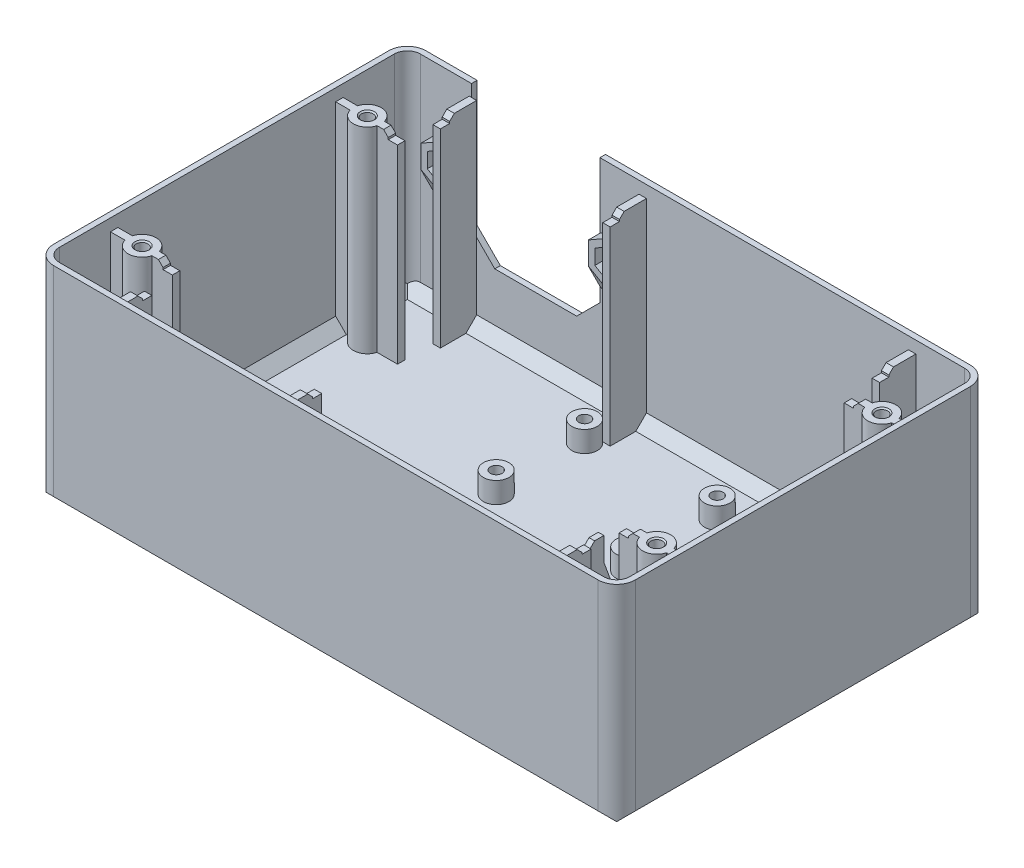
SolidWorks part; units mm, degrees
ref_plane "Ebene vorne" through (0, 0, 0) normal (0, 0, 1) x (1, 0, 0)
ref_plane "Ebene oben" through (0, 0, 0) normal (0, 1, 0) x (1, 0, 0)
ref_plane "Ebene rechts" through (0, 0, 0) normal (1, 0, 0) x (0, 0, -1)
sketch "Skizze1" plane through (0, 0, 0) normal (0, 1, 0) x (1, 0, 0)
  line L1 (-62.5, -40) -> (62.5, -40)
  line L2 (-62.5, -40) -> (-62.5, 40)
  line L3 (-62.5, 40) -> (62.5, 40)
  line L4 (62.5, -40) -> (62.5, 40)
  line L5 (-62.5, -40) -> (62.5, 40) construction
  line L6 (-62.5, 40) -> (62.5, -40) construction
  point P0 (0, 0)
  dimension "D1" = 125
  dimension "D2" = 80
extrude "Aufsatz-Linear austragen1" add sketch "Skizze1" along normal blind 46
fillet "Verrundung1" radius 3 4 edges at (0, 0, -40) (-62.5, 0, 0) (0, 0, 40) (62.5, 0, 0) profile chamfer
fillet "Verrundung2" radius 4 4 edges at (62.5, 24.5, 40) (62.5, 24.5, -40) (-62.5, 24.5, -40) (-62.5, 24.5, 40)
shell "Wandung1" thickness 1.2 removed face at (0, 46, 0)
sketch "Skizze2" plane through (0, 1.2, 0) normal (0, 1, 0) x (1, 0, 0)
  line L0 (31.05, -19.05) -> (31.05, -5.3) construction
  line L1 (14.8, -5.3) -> (47.3, -5.3) construction
  line L2 (14.8, -5.3) -> (14.8, -32.8) construction
  line L3 (14.8, -32.8) -> (47.3, -32.8) construction
  line L4 (47.3, -5.3) -> (47.3, -32.8) construction
  line L5 (14.8, -5.3) -> (47.3, -32.8) construction
  line L6 (14.8, -32.8) -> (47.3, -5.3) construction
  line L7 (20.85, -2.3) -> (22.05, -2.3)
  line L8 (20.85, -2.3) -> (20.85, -5.3)
  line L9 (20.85, -5.3) -> (22.05, -5.3)
  line L10 (22.05, -2.3) -> (22.05, -5.3)
  line L11 (31.05, -19.05) -> (14.8, -19.05) construction
  line L12 (61.3, -38.8) -> (61.3, 38.8) construction
  line L13 (-61.3, -38.8) -> (61.3, -38.8) construction
  line L14 (41.25, -5.3) -> (40.05, -5.3)
  line L15 (41.25, -2.3) -> (41.25, -5.3)
  line L16 (40.05, -2.3) -> (40.05, -5.3)
  line L17 (41.25, -2.3) -> (40.05, -2.3)
  line L18 (50.3, -18.45) -> (50.3, -19.65)
  line L19 (14.8, -18.45) -> (11.8, -18.45)
  line L20 (14.8, -18.45) -> (14.8, -19.65)
  line L21 (14.8, -19.65) -> (11.8, -19.65)
  line L22 (11.8, -18.45) -> (11.8, -19.65)
  line L23 (47.3, -18.45) -> (47.3, -19.65)
  line L24 (47.3, -19.65) -> (50.3, -19.65)
  line L25 (47.3, -18.45) -> (50.3, -18.45)
  line L26 (41.25, -35.8) -> (40.05, -35.8)
  line L27 (40.05, -35.8) -> (40.05, -32.8)
  line L28 (41.25, -35.8) -> (41.25, -32.8)
  line L29 (41.25, -32.8) -> (40.05, -32.8)
  line L30 (22.05, -35.8) -> (22.05, -32.8)
  line L31 (20.85, -32.8) -> (22.05, -32.8)
  line L32 (20.85, -35.8) -> (20.85, -32.8)
  line L33 (20.85, -35.8) -> (22.05, -35.8)
  point P0 (31.05, -19.05)
  dimension "D1" = 1.2
  dimension "D2" = 3
  dimension "D3" = 18
  dimension "D4" = 32.5
  dimension "D5" = 27.5
  dimension "D6" = 14
  dimension "D7" = 6
extrude "Aufsatz-Linear austragen2" add sketch "Skizze2" along normal blind 16
sketch "Skizze3" plane through (0, 0, 19.65) normal (0, 0, 1) x (1, 0, 0)
  line L0 (50.3, 17.2) -> (61.3, 11.2)
  line L1 (61.3, 46) -> (61.3, 1.2) construction
  dimension "D1" = 6
rib "Verstärkungsrippe1" sketch "Skizze3" sketch "Skizze3" thickness 1.2 extrusion direction parallel to sketch draft on no parameters "D1"=1.2
sketch "Skizze4" plane through (41.25, 0, 0) normal (1, 0, 0) x (0, 0, -1)
  line L0 (-35.8, 17.2) -> (-38.8, 11.2)
  line L1 (-38.8, 46) -> (-38.8, 1.2) construction
  dimension "D1" = 6
rib "Verstärkungsrippe3" sketch "Skizze4" sketch "Skizze4" thickness 1.2 extrusion direction parallel to sketch draft on no parameters "D1"=1.2
sketch "Skizze6" plane through (0, 1.2, 0) normal (0, 1, 0) x (1, 0, 0)
  line L0 (15.3, 9.8) -> (-13.2, 9.8) construction
  line L1 (-13.2, 9.8) -> (-13.2, 28.8) construction
  line L2 (-13.2, 28.8) -> (15.3, 28.8) construction
  line L3 (15.3, 28.8) -> (15.3, 9.8) construction
  line L4 (58.5, 38.8) -> (-58.5, 38.8) construction
  line L5 (61.3, -18.45) -> (61.3, 36) construction
  circle A0 centre (-13.2, 9.8) radius 2.75
  circle A1 centre (-13.2, 28.8) radius 2.75
  circle A2 centre (15.3, 9.8) radius 2.75
  circle A3 centre (15.3, 28.8) radius 2.75
  dimension "D3" = 5.5
  dimension "D1" = 19
  dimension "D2" = 10
  dimension "D4" = 46
  dimension "D5" = 28.5
extrude "Aufsatz-Linear austragen3" add sketch "Skizze6" along normal blind 4.5
hole_wizard "M3 Gewindebohrung1" positions "Skizze7" profile "Skizze8" tap size "M3" standard "DIN"
sketch "Skizze7" plane through (0, 5.7, 0) normal (0, 1, 0) x (1, 0, 0)
  point P0 (-13.2, 9.8)
  point P3 (-13.2, 28.8)
  point P6 (15.3, 9.8)
  point P9 (15.3, 28.8)
sketch "Skizze8" plane through (-13.2, 5.7, -9.8) normal (1, 0, 0) x (0, 0, 1)
  line L0 (0, 0) -> (0, 5.2511)
  line L1 (0, 5.2511) -> (1.25, 4.5)
  line L2 (1.25, 4.5) -> (1.25, 0)
  line L5 (1.25, 0) -> (0, 0)
  line L10 (0, 5.2511) -> (-1.25, 4.5) construction
  line L11 (0, -6.35) -> (0, 107.95) construction
  dimension "Bohrerdurchmesser" = 2.5
  dimension "Bohrungstiefe" = 4.5
  dimension "Spitzenwinkel" = 118
cosmetic thread "Bohrungsgewinde1" parameters "D1"=4.5, "D2"=3
cosmetic thread "Bohrungsgewinde2" parameters "D1"=4.5, "D2"=3
cosmetic thread "Bohrungsgewinde3" parameters "D1"=4.5, "D2"=3
cosmetic thread "Bohrungsgewinde4" parameters "D1"=4.5, "D2"=3
sketch "Skizze9" plane through (0, 0, -38.8) normal (0, 0, 1) x (1, 0, 0)
  line L0 (-58.5, 46) -> (58.5, 46) construction
  line L1 (-47.5, 46) -> (-19.9, 46)
  line L2 (-47.5, 46) -> (-47.5, 14)
  line L3 (-47.5, 14) -> (-19.9, 14)
  line L4 (-19.9, 46) -> (-19.9, 14)
  line L9 (-58.5, 3) -> (-58.5, 46) construction
  point P10 (-54.2481, 52.9401)
  dimension "D1" = 27.6
  dimension "D2" = 11
  dimension "D3" = 32
extrude "Schnitt-Linear austragen1" cut sketch "Skizze9" against normal up to next
chamfer "Fase1" distance 5 angle 45 2 edges at (-19.9, 14, -39.4) (-47.5, 14, -39.4)
hole_wizard "Durchgangsloch für M31" positions "Skizze10" profile "Skizze11" hole size "M3" standard "DIN" end condition up to next
sketch "Skizze10" plane through (0, 0, -40) normal (0, 0, 1) x (1, 0, 0)
  point P0 (-51.7, 29.5)
  point P2 (-15.7, 29.5)
  point P15 (-14.7, 23.5)
  point P17 (-50.7, 23.5)
sketch "Skizze11" plane through (-51.7, 29.5, -40) normal (1, 0, 0) x (0, 1, 0)
  line L0 (0, 0) -> (0, 1.2)
  line L1 (0, 1.2) -> (1.7, 1.2)
  line L2 (1.7, 1.2) -> (1.7, 0)
  line L5 (1.7, 0) -> (0, 0)
  line L11 (0, -6.35) -> (0, 107.95) construction
  dimension "Bohrerdurchmesser" = 3.4
  dimension "Bohrungstiefe" = 1.2
sketch "Skizze12" plane through (0, 0, -38.8) normal (0, 0, -1) x (-1, 0, 0)
  line L1 (18.5, 27.8834) -> (18.5, 31.1166)
  line L2 (18.5, 31.1166) -> (15.7, 32.7332)
  line L3 (15.7, 32.7332) -> (12.9, 31.1166)
  line L4 (12.9, 31.1166) -> (12.9, 27.8834)
  line L5 (12.9, 27.8834) -> (15.7, 26.2668)
  line L6 (15.7, 26.2668) -> (18.5, 27.8834)
  line L7 (19.9, 19) -> (19.9, 46) construction
  line L8 (19.9, 31.9249) -> (15.7, 34.3497)
  line L9 (15.7, 34.3497) -> (11.5, 31.9249)
  line L10 (11.5, 31.9249) -> (11.5, 27.0751)
  line L11 (11.5, 27.0751) -> (15.7, 24.6503)
  line L12 (15.7, 24.6503) -> (19.9, 27.0751)
  line L13 (19.9, 27.0751) -> (19.9, 31.9249)
  circle A0 centre (15.7, 29.5) radius 2.8 construction
  circle A1 centre (15.7, 29.5) radius 4.2 construction
  dimension "D1" = 5.6
extrude "Aufsatz-Linear austragen4" add sketch "Skizze12" against normal blind 2.5
ref_plane "Ebene2" through (-33.7, 0, 0) normal (1, 0, 0) x (0, 0, -1)
mirror "Spiegeln2" about plane through (-33.7, 0, 0) normal (1, 0, 0) of "Aufsatz-Linear austragen4"
ref_plane "Ebene3" through (0, 42, 0) normal (0, 1, 0) x (1, 0, 0)
sketch "Skizze14" plane through (0, 42, 0) normal (0, 1, 0) x (1, 0, 0)
  line L0 (-61.3, 36) -> (-61.3, -36) construction
  line L1 (50, 33) -> (-50, 33) construction
  line L2 (50, 33) -> (50, -33) construction
  line L3 (50, -33) -> (-50, -33) construction
  line L4 (-50, 33) -> (-50, -33) construction
  line L5 (50, 33) -> (-50, -33) construction
  line L6 (50, -33) -> (-50, 33) construction
  line L7 (-48, -25) -> (-61.3, -25)
  line L8 (-48, -25) -> (-48, -23.4)
  line L9 (-48, -23.4) -> (-61.3, -23.4)
  line L10 (-61.3, -25) -> (-61.3, -23.4)
  line L11 (0, 0) -> (-50, 0) construction
  line L12 (0, 0) -> (0, -33) construction
  line L17 (-58.5, -38.8) -> (58.5, -38.8) construction
  line L18 (-46.4, -38.8) -> (-48, -38.8)
  line L19 (-46.4, -38.8) -> (-46.4, -31)
  line L20 (-46.4, -31) -> (-48, -31)
  line L21 (-48, -38.8) -> (-48, -31)
  line L23 (-11.5, 36.3) -> (-11.5, 38.8) construction
  line L24 (-9.9, -38.8) -> (-11.5, -38.8)
  line L25 (-9.9, -38.8) -> (-9.9, -31)
  line L26 (-9.9, -31) -> (-11.5, -31)
  line L27 (-11.5, -38.8) -> (-11.5, -31)
  line L28 (-58.5, -38.8) -> (58.5, -38.8) construction
  line L29 (46.4, -31) -> (48, -31)
  line L30 (48, -38.8) -> (48, -31)
  line L31 (46.4, -38.8) -> (48, -38.8)
  line L32 (46.4, -38.8) -> (46.4, -31)
  line L33 (61.3, -25) -> (61.3, -23.4)
  line L34 (48, -23.4) -> (61.3, -23.4)
  line L35 (48, -25) -> (48, -23.4)
  line L36 (48, -25) -> (61.3, -25)
  point P0 (0, 0)
  dimension "D1" = 100
  dimension "D2" = 66
  dimension "D3" = 2
  dimension "D4" = 8
  dimension "D5" = 1.6
  dimension "D6" = 2
  dimension "D7" = 2
extrude "Aufsatz-Linear austragen5" add sketch "Skizze14" against normal up to next
sketch "Skizze15" plane through (0, 42, 0) normal (0, 1, 0) x (1, 0, 0)
  line L0 (46.4, -38.8) -> (46.4, -31) construction
  line L1 (48, -38.8) -> (46.4, -38.8)
  line L2 (48, -38.8) -> (48, -33)
  line L3 (48, -33) -> (46.4, -33)
  line L4 (46.4, -38.8) -> (46.4, -33)
  line L5 (50, -33) -> (-50, -33) construction
  line L6 (-11.5, -38.8) -> (-11.5, -31) construction
  line L7 (-9.9, -38.8) -> (-11.5, -38.8)
  line L8 (-9.9, -38.8) -> (-9.9, -33)
  line L9 (-9.9, -33) -> (-11.5, -33)
  line L10 (-11.5, -38.8) -> (-11.5, -33)
  line L11 (-48, -38.8) -> (-48, -31) construction
  line L12 (-46.4, -38.8) -> (-48, -38.8)
  line L13 (-46.4, -38.8) -> (-46.4, -33)
  line L14 (-46.4, -33) -> (-48, -33)
  line L15 (-48, -38.8) -> (-48, -33)
  line L16 (-48, -25) -> (-61.3, -25) construction
  line L17 (-50, -25) -> (-61.3, -25)
  line L18 (-50, -25) -> (-50, -23.4)
  line L19 (-50, -23.4) -> (-61.3, -23.4)
  line L20 (-61.3, -25) -> (-61.3, -23.4)
  line L21 (-50, 33) -> (-50, -33) construction
  line L22 (48, -23.4) -> (61.3, -23.4) construction
  line L23 (61.3, -25) -> (50, -25)
  line L24 (61.3, -25) -> (61.3, -23.4)
  line L25 (61.3, -23.4) -> (50, -23.4)
  line L26 (50, -25) -> (50, -23.4)
  line L27 (50, 33) -> (50, -33) construction
extrude "Aufsatz-Linear austragen6" add sketch "Skizze15" along normal blind 1.4
chamfer "Fase2" distance 1 angle 45 5 edges at (-50, 43.4, 24.2) (-47.2, 43.4, 33) (-10.7, 43.4, 33) (47.2, 43.4, 33) (50, 43.4, 24.2)
mirror "Spiegeln3" about plane through (0, 0, 0) normal (0, 0, 1) of "Fase2", "Aufsatz-Linear austragen5", "Aufsatz-Linear austragen6"
ref_plane "Ebene1" through (31.05, 0, 0) normal (1, 0, 0) x (0, 0, -1)
sketch "Skizze16" plane through (41.25, 0, 0) normal (1, 0, 0) x (0, 0, -1)
  line L2 (-2.3, 12.2) -> (1.7, 1.2)
  line L4 (23.4, 1.2) -> (-18.45, 1.2) construction
  line L5 (-2.3, 17.2) -> (-2.3, 1.2) construction
  dimension "D1" = 5
  dimension "D2" = 4
rib "Verstärkungsrippe4" sketch "Skizze16" sketch "Skizze16" thickness 1.2 extrusion direction parallel to sketch draft on no parameters "D1"=1.2
sketch "Skizze17" plane through (0, 0, 18.45) normal (0, 0, -1) x (-1, 0, 0)
  line L0 (-11.8, 17.2) -> (0.2, 1.2)
  line L1 (-40.05, 1.2) -> (9.9, 1.2) construction
  dimension "D1" = 12
rib "Verstärkungsrippe5" sketch "Skizze17" sketch "Skizze17" thickness 1.2 extrusion direction parallel to sketch draft on no parameters "D1"=1.2
chamfer "Fase3" distance 1 angle 45 6 edges at (14.8, 17.2, 19.05) (21.45, 17.2, 32.8) (40.65, 17.2, 32.8) (47.3, 17.2, 19.05) (21.45, 17.2, 5.3) (40.65, 17.2, 5.3)
mirror "Spiegeln1" about plane through (31.05, 0, 0) normal (1, 0, 0) of "Verstärkungsrippe3", "Verstärkungsrippe4"
sketch "Skizze18" plane through (-62.5, 0, 0) normal (-1, 0, 0) x (0, 0, 1)
  line L0 (0, 0) -> (0, 46) construction
  line L1 (-36, 46) -> (36, 46) construction
  line L2 (8, 23.8769) -> (8, 46)
  line L3 (8, 46) -> (-8, 46)
  line L4 (-8, 23.8769) -> (-8, 46)
  arc A0 (-8, 23.8769) -> (8, 23.8769) centre (0, 28) ccw
  dimension "D1" = 9
  dimension "D2" = 8
  dimension "D3" = 18
extrude "Schnitt-Linear austragen2" [suppressed] cut sketch "Skizze18" against normal up to next
sketch "Skizze19" plane through (0, 43.4, 0) normal (0, 1, 0) x (1, 0, 0)
  line L0 (-61.3, -24.2) -> (-55.3, -24.2) construction
  line L1 (-61.3, -23.4) -> (-61.3, -25) construction
  line L2 (-61.3, 24.2) -> (-55.3, 24.2) construction
  line L3 (-61.3, 23.4) -> (-61.3, 25) construction
  line L4 (-55.3, 24.2) -> (-55.3, -24.2) construction
  line L5 (55.3, -24.2) -> (61.3, -24.2) construction
  line L6 (61.3, -25) -> (61.3, -23.4) construction
  line L7 (61.3, 24.2) -> (55.3, 24.2) construction
  line L8 (61.3, 25) -> (61.3, 23.4) construction
  line L9 (55.3, -24.2) -> (55.3, 24.2) construction
  circle A0 centre (-55.3, -24.2) radius 3
  circle A1 centre (-55.3, 24.2) radius 3
  circle A2 centre (55.3, 24.2) radius 3
  circle A3 centre (55.3, -24.2) radius 3
  dimension "D2" = 6
  dimension "D1" = 6
extrude "Aufsatz-Linear austragen7" add sketch "Skizze19" against normal up to surface (42.2 mm away) up to face at (21.45, 1.2, 1.8)
hole_wizard "M3 Gewindebohrung2" positions "Skizze20" profile "Skizze21" tap size "M3" standard "DIN"
sketch "Skizze20" plane through (0, 43.4, 0) normal (0, 1, 0) x (1, 0, 0)
  point P0 (55.3, -24.2)
  point P3 (55.3, 24.2)
  point P6 (-55.3, 24.2)
  point P9 (-55.3, -24.2)
sketch "Skizze21" plane through (55.3, 43.4, 24.2) normal (1, 0, 0) x (0, 0, 1)
  line L0 (0, 0) -> (0, 20.7511)
  line L1 (0, 20.7511) -> (1.25, 20)
  line L2 (1.25, 20) -> (1.25, 0.275)
  line L3 (1.25, 0.275) -> (1.525, 0)
  line L5 (1.525, 0) -> (0, 0)
  line L6 (-1.25, 0.275) -> (-1.525, 0) construction
  line L10 (0, 20.7511) -> (-1.25, 20) construction
  line L11 (0, -6.35) -> (0, 107.95) construction
  dimension "Bohrerdurchmesser" = 2.5
  dimension "Bohrungstiefe" = 20
  dimension "Senkdurchmesser (Oben)" = 3.05
  dimension "Senkwinkel (Oben)" = 90
  dimension "Spitzenwinkel" = 118
cosmetic thread "Bohrungsgewinde5" parameters "D1"=15, "D2"=3
cosmetic thread "Bohrungsgewinde6" parameters "D1"=15, "D2"=3
cosmetic thread "Bohrungsgewinde7" parameters "D1"=15, "D2"=3
cosmetic thread "Bohrungsgewinde8" parameters "D1"=15, "D2"=3
draft "Formschräge1" type of draft neutral plane draft angle 60 faces to draft 4 face at (-53.8, 25.8627, -37.55) face at (-49.85, 25.7184, -37.55) face at (-13.6, 25.8627, -37.55) face at (-17.8, 25.8627, -37.55) neutral plane through (0, 0, -36.3) neutral plane normal (0, 0, 1) parameters "D1"=60
